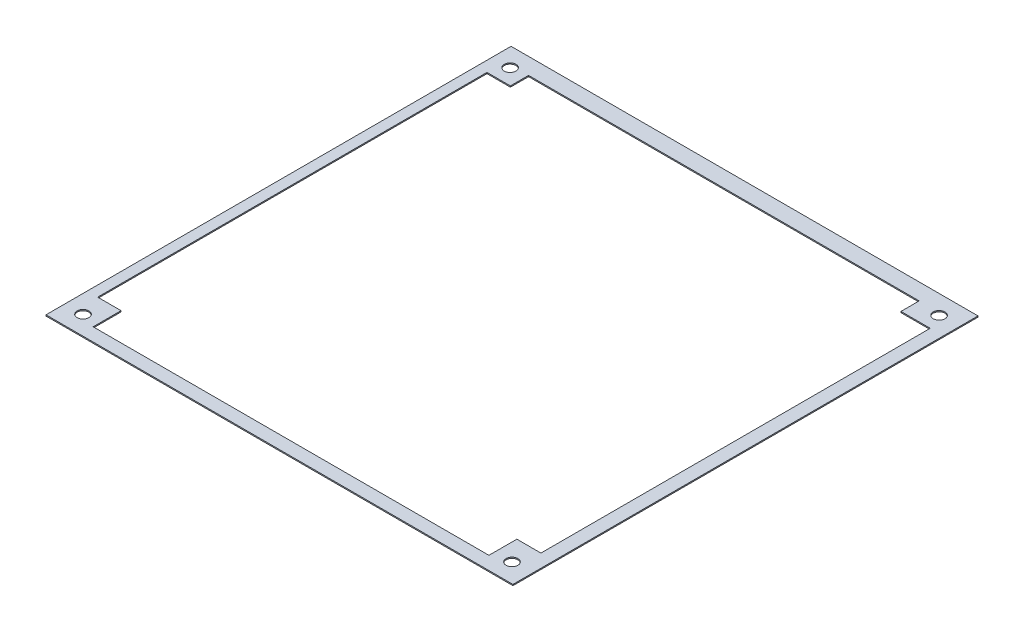
SolidWorks part; units mm, degrees
note: The reader was unsure of these and kept them because the rebuilt part matched: shared geometry of "Sketch2<3>".
ref_plane "Front Plane" through (0, 0, 0) normal (0, 0, 1) x (1, 0, 0)
ref_plane "Top Plane" through (0, 0, 0) normal (0, 1, 0) x (1, 0, 0)
ref_plane "Right Plane" through (0, 0, 0) normal (1, 0, 0) x (0, 0, -1)
sketch "Sketch1" plane through (0, 0, 0) normal (0, 1, 0) x (1, 0, 0)
  line L0 (-6, -6) -> (-6, 106.4)
  line L1 (0, 0) -> (100.4, 0)
  line L2 (0, 0) -> (0, 100.4)
  line L3 (0, 100.4) -> (7.7, 100.4)
  line L4 (100.4, 0) -> (100.4, 40.9)
  line L5 (-6, 106.4) -> (7.7, 106.4)
  line L6 (106.4, -6) -> (106.4, 40.9)
  line L7 (-6, -6) -> (106.4, -6)
  line L8 (100.4, 0) -> (100.4, 100.4) construction
  line L9 (50.2, 100.4) -> (50.2, 0) construction
  line L10 (100.4, 50.2) -> (0, 50.2) construction
  line L11 (92.7, 100.4) -> (92.7, 106.4)
  line L12 (7.7, 100.4) -> (7.7, 106.4)
  line L13 (92.7, 100.4) -> (100.4, 100.4)
  line L14 (0, 100.4) -> (100.4, 100.4) construction
  line L15 (92.7, 106.4) -> (106.4, 106.4)
  line L16 (-6, 106.4) -> (106.4, 106.4) construction
  line L17 (100.4, 59.5) -> (106.4, 59.5)
  line L18 (100.4, 40.9) -> (106.4, 40.9)
  line L19 (100.4, 59.5) -> (100.4, 100.4)
  line L20 (106.4, 59.5) -> (106.4, 106.4)
  line L21 (106.4, -6) -> (106.4, 106.4) construction
  dimension "D1" = 100.4
  dimension "D2" = 100.4
  dimension "D4" = 85
  dimension "D5" = 42.5
  dimension "D6" = 18.6
  dimension "D7" = 9.3
  dimension "D3" = 6
extrude "Boss-Extrude1" add sketch "Sketch1" along normal blind 5.5
sketch "Sketch2" plane through (0, 0, 0) normal (0, -1, 0) x (1, 0, 0)
  line L0 (0, -100.4) -> (7.7, -100.4) construction
  line L1 (-36, 109.6) -> (210, 109.6)
  line L2 (-36, 109.6) -> (-36, -135.4)
  line L3 (-36, -135.4) -> (210, -135.4)
  line L4 (210, 109.6) -> (210, -135.4)
  line L5 (0, 0) -> (0, -100.4) construction
  line L6 (106.4, -106.4) -> (92.7, -106.4) construction
  line L7 (-6, 6) -> (106.4, 6)
  line L8 (-6, 6) -> (-6, -106.4)
  line L9 (-6, -106.4) -> (106.4, -106.4)
  line L10 (106.4, 6) -> (106.4, -106.4)
  dimension "D1" = 246
  dimension "D2" = 245
  dimension "D3" = 210
  dimension "D4" = 210
extrude "Boss-Extrude2" add sketch "Sketch2" along normal blind 9.4 contours L10 L9 L8 L7
extrude "Boss-Extrude3" add sketch "Sketch2<3>" along normal blind 6 from surface at 9.4 contours L2 L3 L4 L1 starting at face at (50.2, -9.4, -50.2)
sketch "Sketch2<3>" plane through (0, 0, 0) normal (0, -1, 0) x (1, 0, 0) same geometry as "Sketch2"
sketch "Sketch3" plane through (0, -9.4, 0) normal (0, 1, 0) x (1, 0, 0)
  line L0 (-36, 135.4) -> (210, 135.4) construction
  line L1 (87, 135.4) -> (87, -109.6) construction
  line L2 (-36, -109.6) -> (210, -109.6) construction
  line L3 (210, 12.9) -> (-36, 12.9) construction
  line L4 (210, -109.6) -> (210, 135.4) construction
  line L5 (-36, -109.6) -> (-36, 135.4) construction
  circle A0 centre (-26.5, 125.4) radius 3.1
  circle A3 centre (-26.5, -99.6) radius 3.1
  circle A4 centre (199.5, 125.4) radius 3.1
  circle A5 centre (199.5, -99.6) radius 3.1
  dimension "D1" = 6.2
  dimension "D5" = 112.5
  dimension "D7" = 112.5
  dimension "D2" = 113.5
  dimension "D3" = 112.5
  dimension "D4" = 112.5
  dimension "D6" = 112.5
extrude "Cut-Extrude1" cut sketch "Sketch3" against normal through all
sketch "Sketch4" plane through (0, -9.4, 0) normal (0, 1, 0) x (1, 0, 0)
  line L0 (-6, -6) -> (106.4, -6) construction
  line L1 (-16, -109.6) -> (49, -109.6)
  line L2 (-36, -89.6) -> (-36, -6)
  line L3 (-36, -6) -> (49, -6)
  line L4 (49, -109.6) -> (49, -6)
  line L5 (-36, -109.6) -> (210, -109.6) construction
  line L8 (-36, -89.6) -> (-22, -89.6)
  line L9 (-16, -109.6) -> (-16, -95.6)
  line L10 (-36, -109.6) -> (-36, 135.4) construction
  arc A0 (-22, -89.6) -> (-16, -95.6) centre (-22, -95.6) cw
  point P15 (-16, -89.6)
  dimension "D4" = 6
  dimension "D1" = 85
  dimension "D2" = 20
  dimension "D3" = 20
extrude "Boss-Extrude4" add sketch "Sketch4" along normal blind 15
sketch "Sketch5" plane through (0, 0, -106.4) normal (0, 0, -1) x (-1, 0, 0)
  line L0 (-107.9, -9.4) -> (-107.9, 13.1)
  line L1 (-8.5, -9.4) -> (7.5, -9.4)
  line L2 (-8.5, -9.4) -> (-8.5, 13.1)
  line L3 (-8.5, 13.1) -> (7.5, 13.1)
  line L4 (7.5, -9.4) -> (7.5, 13.1)
  line L5 (36, -9.4) -> (-210, -9.4) construction
  line L6 (6, 5.5) -> (6, -9.4) construction
  line L7 (-91.9, 13.1) -> (-107.9, 13.1)
  line L8 (-50.2, 0) -> (-50.2, -9.4) construction
  line L9 (-7.7, 0) -> (-92.7, 0) construction
  line L10 (6, -9.4) -> (-106.4, -9.4) construction
  line L11 (-91.9, -9.4) -> (-91.9, 13.1)
  line L12 (-91.9, -9.4) -> (-107.9, -9.4)
  dimension "D1" = 16
  dimension "D2" = 22.5
  dimension "D3" = 14.5
extrude "Boss-Extrude5" add sketch "Sketch5" along normal blind 3.9
sketch "Sketch6" plane through (0, 0, -110.3) normal (0, 0, -1) x (-1, 0, 0)
  line L0 (-8.5, 13.1) -> (-8.5, -9.4) construction
  line L1 (-8.5, 11.1) -> (7.5, 11.1)
  line L2 (-8.5, 11.1) -> (-8.5, -9.4)
  line L3 (-8.5, -9.4) -> (7.5, -9.4)
  line L4 (7.5, 11.1) -> (7.5, -9.4)
  line L5 (7.5, 13.1) -> (-8.5, 13.1) construction
  line L6 (-50.2, 0) -> (-50.2, -9.4) construction
  line L7 (-8.5, 0) -> (-91.9, 0) construction
  line L8 (-8.5, -9.4) -> (-91.9, -9.4) construction
  line L9 (-107.9, 11.1) -> (-107.9, -9.4)
  line L10 (-91.9, -9.4) -> (-107.9, -9.4)
  line L11 (-91.9, 11.1) -> (-91.9, -9.4)
  line L12 (-91.9, 11.1) -> (-107.9, 11.1)
  dimension "D1" = 2
extrude "Cut-Extrude2" cut sketch "Sketch6" against normal blind 3.4
chamfer "Chamfer1" distance 2 angle 45 8 edges at (99.9, 13.1, -106.4) (92.7, 2.75, -106.4) (99.55, 5.5, -106.4) (106.4, -1.95, -106.4) (0.5, 13.1, -106.4) (7.7, 2.75, -106.4) (0.85, 5.5, -106.4) (-6, -1.95, -106.4)
chamfer "Chamfer2" distance 3.05 angle 45 4 edges at (199.5, -9.4, -122.3) (-26.5, -9.4, -122.3) (-26.5, -9.4, 96.5) (199.5, -9.4, 102.7)
chamfer "Chamfer3" distance 3 angle 45 11 edges at (106.4, 5.5, -81.95) (-6, 5.5, -49.2) (6.5, 5.6, 6) (-36, 5.6, 47.8) (-29, 5.6, 89.6) (-16, 5.6, 102.6) (-17.7574, 5.6, 91.3574) (106.4, 5.5, -17.45) (77.7, 5.5, 6) (49, 5.6, 57.8) (16.5, 5.6, 109.6)
chamfer "Chamfer4" distance 3 angle 45 11 edges at (-36, -9.4, -64.7) (129.5, -9.4, 109.6) (-36, -3.4, 89.6) (-36, -3.4, 6) (-34.5, 4.1, 6) (-16, -3.4, 109.6) (49, -3.4, 109.6) (-36, -9.4, 99.6) (87, -9.4, -135.4) (-26, -9.4, 109.6) (210, -9.4, -12.9)
sketch "Sketch8" plane through (0, 5.6, 0) normal (0, 1, 0) x (1, 0, 0)
  line L0 (-33, -6) -> (-33, -86.6) construction
  line L1 (46.1, -6) -> (-33, -6)
  line L2 (46.1, -6) -> (46.1, -11)
  line L3 (46.1, -11) -> (-33, -11)
  line L4 (-33, -6) -> (-33, -11)
  dimension "D1" = 5
extrude "Cut-Extrude3" cut sketch "Sketch8" against normal blind 0.1
chamfer "Chamfer5" distance 3 angle 45 1 edges at (-18, 5.5, 6)
sketch "Sketch9" plane through (0, 0, 109.6) normal (0, 0, 1) x (1, 0, 0)
  line L0 (-36, -15.4) -> (-36, -12.4) construction
  line L1 (-36, -14.8) -> (210, -14.8)
  line L2 (-36, -14.8) -> (-36, 13.1)
  line L3 (-36, 13.1) -> (210, 13.1)
  line L4 (210, -14.8) -> (210, 13.1)
  line L5 (210, -15.4) -> (210, -12.4) construction
  line L6 (91.9, 13.1) -> (107.9, 13.1) construction
  line L7 (-36, -15.4) -> (210, -15.4) construction
  dimension "D1" = 0.6
extrude "Cut-Extrude4" cut sketch "Sketch9" against normal through all
sketch "Sketch10" plane through (0, -14.8, 0) normal (0, 1, 0) x (1, 0, 0)
  line L0 (-13.3203, 126.7447) -> (187.6627, 126.7447)
  line L1 (187.6627, 126.7447) -> (187.6627, 117.1578)
  line L2 (187.6627, 117.1578) -> (203.0702, 117.1578)
  line L3 (203.0702, 117.1578) -> (203.0702, -87.9339)
  line L4 (203.0702, -87.9339) -> (190.4018, -87.9339)
  line L5 (190.4018, -87.9339) -> (190.4018, -102.6566)
  line L6 (190.4018, -102.6566) -> (-18.1137, -102.6566)
  line L7 (-18.1137, -102.6566) -> (-18.1137, -87.9339)
  line L8 (-18.1137, -87.9339) -> (-30.4398, -87.9339)
  line L9 (-30.4398, -87.9339) -> (-30.4398, 117.1578)
  line L10 (-30.4398, 117.1578) -> (-18.1137, 117.1578)
  line L11 (-18.1137, 117.1578) -> (-18.1137, 126.7447)
  line L12 (-18.1137, 126.7447) -> (-13.3203, 126.7447)
extrude "Cut-Extrude5" cut sketch "Sketch10" against normal through all
